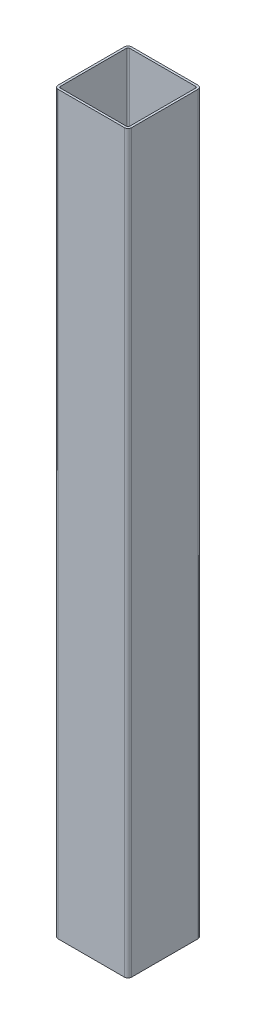
SolidWorks part; units mm, degrees
ref_plane "Спереди" through (0, 0, 0) normal (0, 0, 1) x (1, 0, 0)
ref_plane "Сверху" through (0, 0, 0) normal (0, 1, 0) x (1, 0, 0)
ref_plane "Справа" through (0, 0, 0) normal (1, 0, 0) x (0, 0, -1)
sketch "Эскиз1" plane through (0, 0, 0) normal (0, 1, 0) x (1, 0, 0)
  line L1 (-45, 50) -> (45, 50)
  line L2 (-50, 45) -> (-50, -45)
  line L3 (-45, -50) -> (45, -50)
  line L4 (50, 45) -> (50, -45)
  line L5 (-50, 50) -> (50, -50) construction
  line L6 (-50, -50) -> (50, 50) construction
  arc A0 (45, -50) -> (50, -45) centre (45, -45) ccw
  arc A1 (45, 50) -> (50, 45) centre (45, 45) cw
  arc A2 (-45, 50) -> (-50, 45) centre (-45, 45) ccw
  arc A3 (-50, -45) -> (-45, -50) centre (-45, -45) ccw
  point P0 (0, 0)
  dimension "D3" = 5
  dimension "D1" = 100
  dimension "D2" = 100
extrude "Вытянуть-Тонкостенный1" add sketch "Эскиз1" along normal blind 1000 thin thin type one direction reverse wall 3
